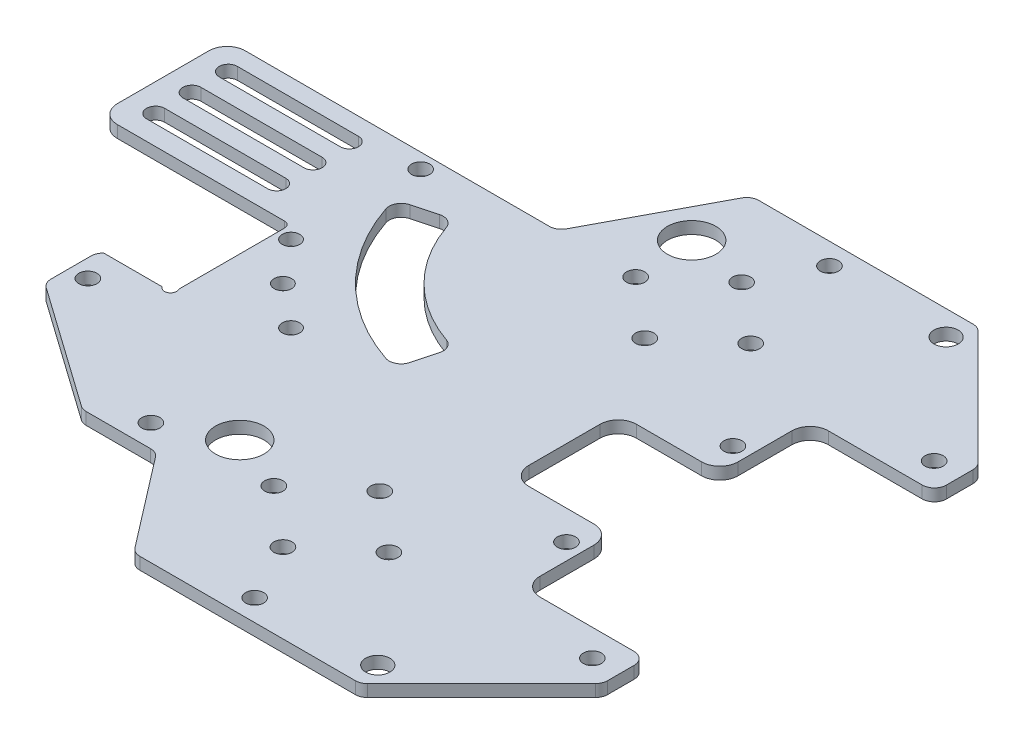
SolidWorks part; units mm, degrees
ref_plane "前视基准面" through (0, 0, 0) normal (0, 0, 1) x (1, 0, 0)
ref_plane "上视基准面" through (0, 0, 0) normal (0, 1, 0) x (1, 0, 0)
ref_plane "右视基准面" through (0, 0, 0) normal (1, 0, 0) x (0, 0, -1)
sketch "Sketch1" plane through (0, 0, 0) normal (0, 1, 0) x (1, 0, 0)
  line L0 (41.0899, -3.4167) -> (-33.1851, -3.4167) construction
  line L7 (54.8692, -12.3054) -> (44.0899, -12.3054)
  line L8 (41.0899, -9.3054) -> (41.0899, 2.4719)
  line L9 (44.0899, 5.4719) -> (54.8692, 5.4719)
  line L10 (57.8692, 8.4719) -> (57.8692, 17.3758)
  line L12 (-13.8687, 26.5833) -> (-44.6204, 26.5833)
  line L14 (-13.8687, 5.4719) -> (-44.6204, 5.4719)
  line L15 (-44.6204, 26.5833) -> (-44.6204, 5.4719)
  line L23 (16.5589, -4.4258) -> (17.5965, -0.5535)
  line L24 (-2.1519, 19.1949) -> (-6.0243, 18.1573)
  line L38 (20.9798, 47.5858) -> (9.813, 26.5833)
  line L39 (9.813, 26.5833) -> (-13.8687, 26.5833)
  line L40 (-13.8687, 5.4719) -> (-13.8687, -11.4447)
  line L41 (-13.8687, -11.4447) -> (-25.0098, -11.4447)
  line L42 (-25.0098, -11.4447) -> (-25.0098, -23.1435)
  line L43 (-25.0098, -23.1435) -> (-3.7966, -38.1435)
  line L44 (-3.7966, -38.1435) -> (8.4645, -38.1435)
  line L45 (8.4645, -38.1435) -> (20.9798, -54.4192)
  line L46 (20.9798, -54.4192) -> (58.3898, -54.4192)
  line L47 (58.3898, -54.4192) -> (78.3898, -34.4192)
  line L48 (78.3898, -34.4192) -> (78.3898, -27.2092)
  line L49 (78.3898, -27.2092) -> (60.8692, -27.2092)
  line L50 (57.8692, -24.2092) -> (57.8692, -15.3054)
  line L51 (60.8692, 20.3758) -> (78.3898, 20.3758)
  line L52 (78.3898, 20.3758) -> (78.3898, 27.5858)
  line L53 (78.3898, 27.5858) -> (58.3898, 47.5858)
  line L54 (58.3898, 47.5858) -> (20.9798, 47.5858)
  arc A4 (57.8692, -24.2092) -> (60.8692, -27.2092) centre (60.8692, -24.2092) ccw
  arc A5 (60.8692, 20.3758) -> (57.8692, 17.3758) centre (60.8692, 17.3758) ccw
  arc A6 (57.8692, -15.3054) -> (54.8692, -12.3054) centre (54.8692, -15.3054) ccw
  arc A7 (41.0899, -9.3054) -> (44.0899, -12.3054) centre (44.0899, -9.3054) ccw
  arc A8 (44.0899, 5.4719) -> (41.0899, 2.4719) centre (44.0899, 2.4719) ccw
  arc A9 (54.8692, 5.4719) -> (57.8692, 8.4719) centre (54.8692, 8.4719) ccw
  circle A10 centre (32.4798, -41.2942) radius 1.5
  circle A11 centre (41.9798, -33.2942) radius 1.5
  circle A12 centre (32.4798, -25.2942) radius 1.5
  circle A13 centre (22.9798, -33.2942) radius 1.5
  arc A17 (13.9897, -5.8039) -> (16.5589, -4.4258) centre (14.6271, -3.9082) ccw
  arc A18 (17.5965, -0.5535) -> (16.319, 1.8541) centre (15.6647, -0.0358) ccw
  arc A19 (0.2557, 17.9174) -> (-2.1519, 19.1949) centre (-1.6343, 17.2631) ccw
  arc A20 (0.2557, 17.9174) -> (16.319, 1.8541) centre (24.8249, 26.4234) ccw
  arc A21 (-6.0243, 18.1573) -> (-7.4024, 15.5881) centre (-5.5066, 16.2255) ccw
  arc A22 (-7.4024, 15.5881) -> (13.9897, -5.8039) centre (24.8249, 26.4234) ccw
  circle A23 centre (-10.1941, 24.1202) radius 1.5
  circle A24 centre (-22.0497, -18.9846) radius 1.5
  circle A25 centre (3.7985, -34.4192) radius 1.5
  circle A26 centre (57.1939, -50.3459) radius 2
  circle A27 centre (55.1743, -17.1595) radius 1.5
  circle A28 centre (55.1743, 10.3261) radius 1.5
  circle A35 centre (-10.8665, 3.389) radius 1.45
  circle A36 centre (-5.2086, -3.6102) radius 1.45
  circle A37 centre (1.7906, -9.268) radius 1.45
  circle A38 centre (57.1939, 43.5124) radius 2
  circle A39 centre (22.9798, 26.4608) radius 1.5
  circle A40 centre (32.4798, 18.4608) radius 1.5
  circle A41 centre (41.9798, 26.4608) radius 1.5
  circle A42 centre (32.4798, 34.4608) radius 1.5
  point P55 (57.1939, 43.5124)
  point P89 (57.1939, 43.7154)
extrude "Boss-Extrude1" add sketch "Sketch1" along normal blind 2
sketch "Sketch2" plane through (0, 0, 0) normal (0, -1, 0) x (1, 0, 0)
  line L0 (-40.0419, -10.2002) -> (-20.0419, -10.2002) construction
  line L1 (-40.0419, -8.7002) -> (-20.0419, -8.7002)
  line L2 (-40.0419, -11.7002) -> (-20.0419, -11.7002)
  line L3 (-40.0419, -17.7002) -> (-20.0419, -17.7002)
  line L6 (-40.0419, -14.7002) -> (-20.0419, -14.7002)
  line L7 (-40.0419, -16.2002) -> (-20.0419, -16.2002) construction
  line L8 (-40.0419, -23.7002) -> (-20.0419, -23.7002)
  line L9 (-40.0419, -20.7002) -> (-20.0419, -20.7002)
  line L10 (-40.0419, -22.2002) -> (-20.0419, -22.2002) construction
  arc A0 (-40.0419, -8.7002) -> (-40.0419, -11.7002) centre (-40.0419, -10.2002) ccw
  arc A1 (-20.0419, -11.7002) -> (-20.0419, -8.7002) centre (-20.0419, -10.2002) ccw
  arc A4 (-40.0419, -14.7002) -> (-40.0419, -17.7002) centre (-40.0419, -16.2002) ccw
  arc A5 (-20.0419, -17.7002) -> (-20.0419, -14.7002) centre (-20.0419, -16.2002) ccw
  arc A6 (-40.0419, -20.7002) -> (-40.0419, -23.7002) centre (-40.0419, -22.2002) ccw
  arc A7 (-20.0419, -23.7002) -> (-20.0419, -20.7002) centre (-20.0419, -22.2002) ccw
  point P2 (-30.0419, -10.2002)
  point P11 (-30.0419, -16.2002)
  point P18 (-30.0419, -22.2002)
  dimension "D1" = 3
extrude "Cut-Extrude1" cut sketch "Sketch2" against normal blind 2
fillet "Fillet1" radius 3 2 edges at (-44.6204, 1, -5.4719) (-44.6204, 1, -26.5833)
sketch "Sketch3" plane through (0, 0, 0) normal (0, -1, 0) x (1, 0, 0)
  circle A4 centre (37.3949, -44.0491) radius 1.5
  circle A5 centre (37.3949, 50.8826) radius 1.5
  circle A6 centre (73.9274, 31.6377) radius 1.5
  circle A7 centre (73.9274, -24.8042) radius 1.5
extrude "Cut-Extrude2" cut sketch "Sketch3" against normal blind 10
sketch "草图1" plane through (0, 0, 0) normal (0, -1, 0) x (1, 0, 0)
  line L0 (-13.8687, 11.4447) -> (-25.0098, 11.4447) construction
  line L1 (-13.8687, 11.4447) -> (-25.0098, 11.4447)
  line L2 (-13.8687, 11.4447) -> (-13.8687, 13.5087)
  line L3 (-13.8687, 13.5087) -> (-25.0098, 13.5087)
  line L4 (-25.0098, 11.4447) -> (-25.0098, 13.5087)
  line L5 (-13.8687, -5.4719) -> (-13.8687, 11.4447) construction
  line L6 (-25.0098, 11.4447) -> (-25.0098, 23.1435) construction
extrude "切除-拉伸1" cut sketch "草图1" against normal blind 10
sketch "草图2" plane through (0, 0, 0) normal (0, -1, 0) x (1, 0, 0)
  line L3 (41.0899, 3.4167) -> (40.3774, 3.4167) construction
  circle A4 centre (13.6015, 29.5432) radius 4
  circle A5 centre (22.3516, -36.3362) radius 4
extrude "切除-拉伸2" cut sketch "草图2" against normal through all
fillet "Fillet2" radius 2 14 edges at (78.3898, 1, -20.3758) (78.3898, 1, -27.5858) (58.3898, 1, -47.5858) (20.9798, 1, -47.5858) (9.813, 1, -26.5833) (78.3898, 1, 34.4192) (78.3898, 1, 27.2092) (58.3898, 1, 54.4192) (20.9798, 1, 54.4192) (8.4645, 1, 38.1435) (-3.7966, 1, 38.1435) (-25.0098, 1, 23.1435) (-25.0098, 1, 13.5087) (-13.8687, 1, -5.4719)
sketch "Sketch4" plane through (0, 2, 0) normal (0, 1, 0) x (1, 0, 0)
  circle A0 centre (-13.8687, -13.5087) radius 1
extrude "Cut-Extrude3" cut sketch "Sketch4" against normal blind 10
sketch "Sketch5" plane through (0, 2, 0) normal (0, 1, 0) x (1, 0, 0)
  line L0 (-41.6204, 5.4719) -> (-15.8687, 5.4719) construction
  line L1 (-24.8426, 5.4719) -> (-13.0152, 5.4719)
  line L2 (-24.8426, 5.4719) -> (-24.8426, -14.0311)
  line L3 (-24.8426, -14.0311) -> (-13.0152, -14.0311)
  line L4 (-13.0152, 5.4719) -> (-13.0152, -14.0311)
extrude "Cut-Extrude4" cut sketch "Sketch5" against normal blind 10
fillet "Fillet3" radius 1 1 edges at (-13.0152, 1, -5.4719)
